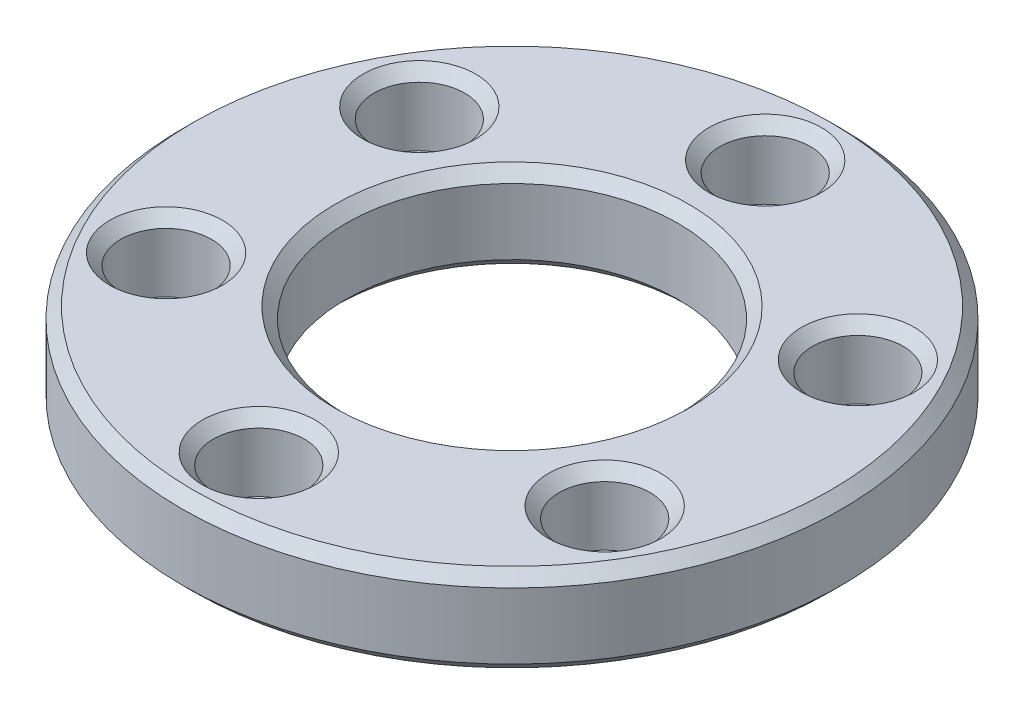
SolidWorks part; units mm, degrees
ref_plane "前视基准面" through (0, 0, 0) normal (0, 0, 1) x (1, 0, 0)
ref_plane "上视基准面" through (0, 0, 0) normal (0, 1, 0) x (1, 0, 0)
ref_plane "右视基准面" through (0, 0, 0) normal (1, 0, 0) x (0, 0, -1)
other "Configuration Table"
sketch "草图1" plane through (0, 0, 0) normal (0, 1, 0) x (1, 0, 0)
  circle A0 centre (0, 0) radius 7.55
  circle A1 centre (0, 0) radius 15
  circle A2 centre (0, 0) radius 11.525 construction
  circle A3 centre (0, 11.525) radius 2.065
  circle A4 centre (9.9809, 5.7625) radius 2.065
  circle A5 centre (9.9809, -5.7625) radius 2.065
  circle A6 centre (0, -11.525) radius 2.065
  circle A7 centre (-9.9809, -5.7625) radius 2.065
  circle A8 centre (-9.9809, 5.7625) radius 2.065
  point P19 (0, 0)
  dimension "D1" = 15.1
  dimension "D2" = 30
  dimension "D3" = 23.05
  dimension "D4" = 4.13
  dimension "D5" = 6
extrude "凸台-拉伸1" add sketch "草图1" along normal blind 3.2
sketch "草图2" plane through (0, 0, 0) normal (0, -1, 0) x (-1, 0, 0)
  circle A0 centre (0, 0) radius 7.55 construction
  circle A1 centre (0, 0) radius 15 construction
  circle A2 centre (0, 0) radius 7.55
  circle A3 centre (0, 0) radius 15
  circle A4 centre (0, 11.53) radius 0.9
  circle A6 centre (0, 0) radius 11.53 construction
  circle A7 centre (9.9853, 5.765) radius 0.9
  circle A8 centre (9.9853, -5.765) radius 0.9
  circle A9 centre (0, -11.53) radius 0.9
  circle A10 centre (-9.9853, -5.765) radius 0.9
  circle A11 centre (-9.9853, 5.765) radius 0.9
  point P21 (0, 0)
  dimension "D1" = 1.8
  dimension "D2" = 23.06
  dimension "D3" = 6
extrude "凸台-拉伸2" add sketch "草图2" along normal blind 0.8
chamfer "倒角1" distance 0.5 angle 45 10 edges at (0, -0.8, -7.55) (0, -0.8, -15) (-9.9809, 3.2, -3.6975) (0, 3.2, 13.59) (9.9809, 3.2, -3.6975) (0, 3.2, 7.55) (0, 3.2, 15) (0, 3.2, -9.46) (9.9809, 3.2, 7.8275) (-9.9809, 3.2, 7.8275)
